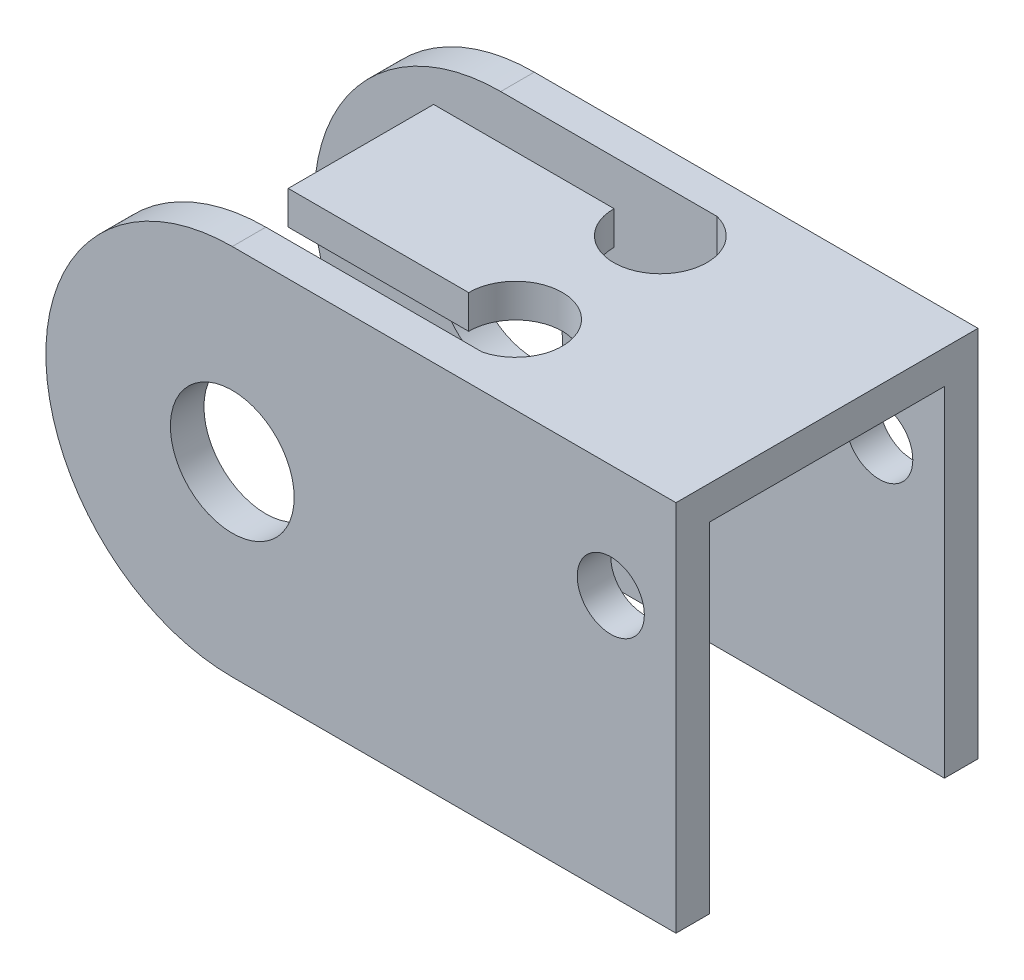
SolidWorks part; units mm, degrees
material "Plain Carbon Steel"
ref_plane "Front Plane" through (0, 0, 0) normal (0, 0, 1) x (1, 0, 0)
ref_plane "Top Plane" through (0, 0, 0) normal (0, 1, 0) x (1, 0, 0)
ref_plane "Right Plane" through (0, 0, 0) normal (1, 0, 0) x (0, 0, -1)
sketch "Sketch1" plane through (0, 0, 0) normal (0, 1, 0) x (1, 0, 0)
  line L1 (-4.0767, 5.1435) -> (4.0767, 5.1435)
  line L2 (-4.0767, 5.1435) -> (-4.0767, -5.1435)
  line L3 (-4.0767, -5.1435) -> (4.0767, -5.1435)
  line L4 (4.0767, 5.1435) -> (4.0767, -5.1435)
  line L5 (-4.0767, 5.1435) -> (4.0767, -5.1435) construction
  line L6 (-4.0767, -5.1435) -> (4.0767, 5.1435) construction
  point P0 (0, 0)
  dimension "D1" = 8.1534
  dimension "D2" = 10.287
extrude "Boss-Extrude1" add sketch "Sketch1" along normal blind 1.143
sketch "Sketch2" plane through (0, 0, 0) normal (0, 1, 0) x (1, 0, 0)
  line L0 (4.0767, -5.1435) -> (4.0767, 5.1435) construction
  line L1 (-11.7983, 2.4765) -> (-5.6515, 2.4765)
  line L2 (-11.7983, 2.4765) -> (-11.7983, -2.4765)
  line L3 (-11.7983, -2.4765) -> (-5.6515, -2.4765)
  line L5 (-11.7983, 2.4765) -> (-5.4096, -1.6215) construction
  line L6 (-11.7983, -2.4765) -> (-5.4096, 1.6215) construction
  line L7 (-4.0767, 5.1435) -> (-4.0767, -5.1435) construction
  line L8 (-4.0767, 5.1435) -> (-4.0767, 4.0513)
  line L10 (-4.0767, -4.0513) -> (-4.0767, -5.1435)
  line L11 (-4.0767, 5.1435) -> (4.0767, 5.1435)
  line L12 (4.0767, 5.1435) -> (4.0767, -5.1435)
  line L13 (4.0767, -5.1435) -> (-4.0767, -5.1435)
  arc A0 (-4.0767, -4.0513) -> (-5.6515, -2.4765) centre (-4.0641, -2.4639) ccw
  arc A1 (-5.6515, 2.4765) -> (-4.0767, 4.0513) centre (-4.0641, 2.4639) ccw
  point P0 (-7.9375, 0)
  dimension "D3" = 1.5875
  dimension "D1" = 4.953
  dimension "D2" = 15.875
  dimension "D4" = 1.5748
  dimension "D5" = 1.5748
  dimension "D6" = 2.667
  dimension "D7" = 1.5748
  dimension "D8" = 7.59
extrude "Boss-Extrude2" add sketch "Sketch2" along normal blind 1.143
sketch "Sketch3" plane through (0, 1.143, 0) normal (0, 1, 0) x (1, 0, 0)
  circle A0 centre (-4.0641, 2.4639) radius 1.5875
  circle A1 centre (-4.0641, -2.4639) radius 1.5875
extrude "Cut-Extrude1" cut sketch "Sketch3" against normal blind 1.143
sketch "Sketch4" plane through (0, 0, 5.1435) normal (0, 0, 1) x (1, 0, 0)
  line L1 (4.0767, 1.143) -> (-17.3863, 1.143)
  line L2 (4.0767, 1.143) -> (4.0767, -11.557)
  line L3 (4.0767, -11.557) -> (-17.3863, -11.557)
  line L4 (-17.3863, 1.143) -> (-17.3863, -11.557)
  dimension "D1" = 21.463
  dimension "D2" = 12.7
extrude "Boss-Extrude3" add sketch "Sketch4" against normal blind 1.143
fillet "Fillet1" 2 edges at (-17.3863, 1.143, 4.572) (-17.3863, -11.557, 4.572) type full round first side face at (-6.3504, 1.143, 0.3489) second side face at (-6.6548, -11.557, 4.572) middle face at (-17.3863, -5.207, 4.572)
hole_wizard "#19 (0.166) Diameter Hole1" positions "Sketch7" profile "Sketch8" hole size "#19" standard "ANSI Inch" end condition through all
sketch "Sketch7" plane through (0, 0, 5.1435) normal (0, 0, 1) x (1, 0, 0)
  point P0 (-11.0363, -5.207)
sketch "Sketch8" plane through (-11.0363, -5.207, 5.1435) normal (1, 0, 0) x (0, -1, 0)
  line L0 (0, 0) -> (0, 10.287)
  line L1 (0, 10.287) -> (2.1082, 10.287)
  line L2 (2.1082, 10.287) -> (2.1082, 0)
  line L5 (2.1082, 0) -> (0, 0)
  line L11 (0, -6.35) -> (0, 107.95) construction
  dimension "Thru Hole Dia." = 4.2164
  dimension "Thru Hole Depth" = 10.287
sketch "Sketch9" plane through (0, 0, 5.1435) normal (0, 0, 1) x (1, 0, 0)
  circle A0 centre (1.8562, -2.7066) radius 1.143
  dimension "D1" = 2.286
extrude "Cut-Extrude2" cut sketch "Sketch9" against normal up to vertex (1.143 mm away) up to point (4.0767, -11.557, 4.0005)
mirror "Mirror1" about plane through (0, 0, 0) normal (0, 0, 1) of "Fillet1", "Boss-Extrude3", "#19 (0.166) Diameter Hole1", "Cut-Extrude2"
